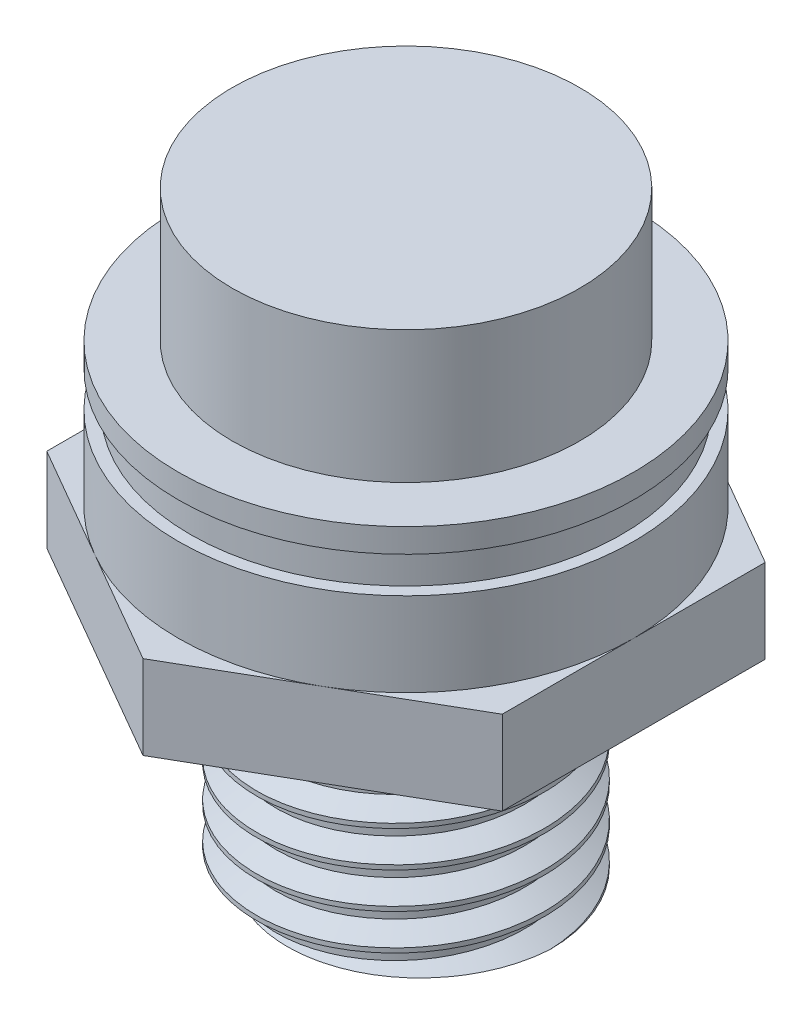
SolidWorks part; units mm, degrees
ref_plane "Front Plane" through (0, 0, 0) normal (0, 0, 1) x (1, 0, 0)
ref_plane "Top Plane" through (0, 0, 0) normal (0, 1, 0) x (1, 0, 0)
ref_plane "Right Plane" through (0, 0, 0) normal (1, 0, 0) x (0, 0, -1)
sketch "Sketch1" plane through (0, 0, 0) normal (0, 1, 0) x (1, 0, 0)
  line L1 (0, 10.9697) -> (-9.5, 5.4848)
  line L2 (-9.5, 5.4848) -> (-9.5, -5.4848)
  line L3 (-9.5, -5.4848) -> (0, -10.9697)
  line L4 (0, -10.9697) -> (9.5, -5.4848)
  line L5 (9.5, -5.4848) -> (9.5, 5.4848)
  line L6 (9.5, 5.4848) -> (0, 10.9697)
  circle A0 centre (0, 0) radius 9.5 construction
  dimension "D1" = 19
extrude "Boss-Extrude1" add sketch "Sketch1" along normal blind 3.5
sketch "Sketch2" plane through (0, 3.5, 0) normal (0, 1, 0) x (1, 0, 0)
  circle A0 centre (0, 0) radius 9.5
  dimension "D1" = 19
extrude "Boss-Extrude2" add sketch "Sketch2" along normal blind 3.5
sketch "Sketch3" plane through (0, 7, 0) normal (0, 1, 0) x (1, 0, 0)
  circle A0 centre (0, 0) radius 9
  dimension "D1" = 18
extrude "Boss-Extrude3" add sketch "Sketch3" along normal blind 1.5
sketch "Sketch4" plane through (0, 8.5, 0) normal (0, 1, 0) x (1, 0, 0)
  circle A0 centre (0, 0) radius 9.5
extrude "Boss-Extrude4" add sketch "Sketch4" along normal blind 1
sketch "Sketch5" plane through (0, 9.5, 0) normal (0, 1, 0) x (1, 0, 0)
  circle A0 centre (0, 0) radius 7.25
  dimension "D1" = 14.5
extrude "Boss-Extrude5" add sketch "Sketch5" along normal blind 5.52
sketch "Sketch6" plane through (0, 0, 0) normal (0, -1, 0) x (1, 0, 0)
  circle A0 centre (0, 0) radius 6
  dimension "D1" = 12
extrude "Boss-Extrude6" add sketch "Sketch6" along normal blind 9.5
sketch "Sketch14" plane through (0, 0, 0) normal (0, -1, 0) x (1, 0, 0)
  circle A0 centre (0, 0) radius 4.5
  circle A1 centre (0, 0) radius 6
  circle A2 centre (0, 0) radius 6 construction
  dimension "D1" = 1.5
extrude "Cut-Extrude1" cut sketch "Sketch14" along normal blind 1.5
thread "Thread1" pitch 1.5 method cut profile "Thread Profile3" start angle 0, offset 1.5, length 9.5, pitch 1.5, diameter 12
ref_plane "Plane3" through (6, -11, 0) normal (0, 0, 1) x (1, 0, 0)
sketch "Thread Profile3" plane through (6, -11, 0) normal (0, 0, 1) x (1, 0, 0)
  line L0 (0, 0) -> (0, 1.5) construction
  line L11 (0, 0) -> (0, 1.3125)
  line L12 (0, 1.3125) -> (-0.8119, 0.8437)
  line L13 (-0.8119, 0.8437) -> (-0.8119, 0.4687)
  line L15 (-0.8119, 0.4687) -> (0, 0)
  line L17 (-0.8119, 0.6562) -> (0, 0.6562) construction
  point P2 (0, 0)
  dimension "Pitch" = 1.5
  dimension "Profile_Angle" = 60
  dimension "Profile_Land" = 0.375
  dimension "Profile_Height" = 0.8119
